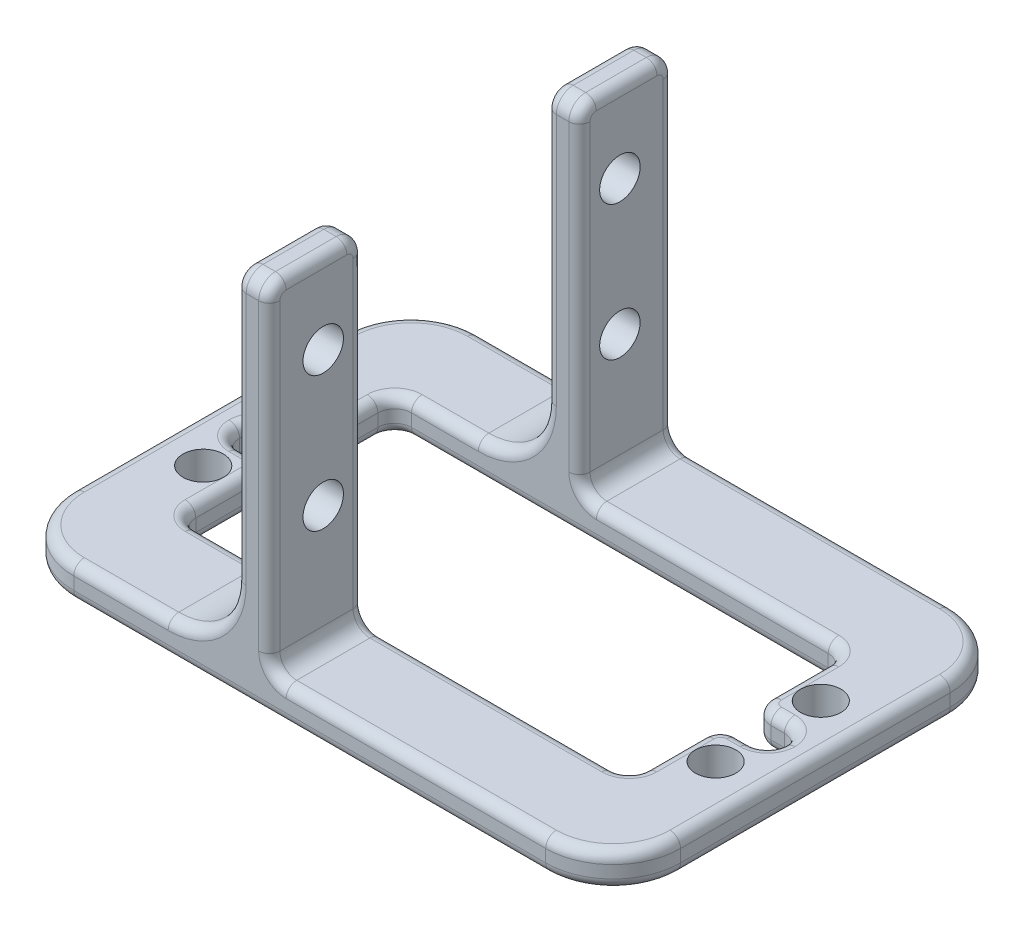
SolidWorks part; units mm, degrees
ref_plane "Front Plane" through (0, 0, 0) normal (0, 0, 1) x (1, 0, 0)
ref_plane "Top Plane" through (0, 0, 0) normal (0, 1, 0) x (1, 0, 0)
ref_plane "Right Plane" through (0, 0, 0) normal (1, 0, 0) x (0, 0, -1)
sketch "Sketch1" plane through (0, 0, 0) normal (0, 1, 0) x (1, 0, 0)
  line L1 (-28.575, -19.05) -> (28.575, -19.05)
  line L2 (-28.575, -19.05) -> (-28.575, 19.05)
  line L3 (-28.575, 19.05) -> (28.575, 19.05)
  line L4 (28.575, -19.05) -> (28.575, 19.05)
  line L5 (-28.575, -19.05) -> (28.575, 19.05) construction
  line L6 (-28.575, 19.05) -> (28.575, -19.05) construction
  point P0 (0, 0)
  dimension "D1" = 38.1
  dimension "D2" = 57.15
extrude "Boss-Extrude1" add sketch "Sketch1" along normal blind 3.175
sketch "Sketch2" plane through (0, 3.175, 0) normal (0, 1, 0) x (1, 0, 0)
  line L0 (0, 0) -> (-28.575, 0) construction
  line L1 (-24.13, -4.953) -> (24.13, -4.953) construction
  line L2 (-24.13, -4.953) -> (-24.13, 4.953) construction
  line L3 (-24.13, 4.953) -> (24.13, 4.953) construction
  line L4 (24.13, -4.953) -> (24.13, 4.953) construction
  line L5 (-24.13, -4.953) -> (24.13, 4.953) construction
  line L6 (-24.13, 4.953) -> (24.13, -4.953) construction
  line L7 (-21.209, -10.16) -> (21.209, -10.16)
  line L8 (-21.209, -10.16) -> (-21.209, 10.16) construction
  line L9 (-21.209, 10.16) -> (21.209, 10.16)
  line L10 (21.209, -10.16) -> (21.209, 10.16) construction
  line L11 (-21.209, -10.16) -> (21.209, 10.16) construction
  line L12 (-21.209, 10.16) -> (21.209, -10.16) construction
  line L13 (-28.575, 19.05) -> (-28.575, -19.05) construction
  line L14 (-28.575, 0) -> (28.575, 0) construction
  line L15 (28.575, -19.05) -> (28.575, 19.05) construction
  line L16 (21.209, -1.5875) -> (21.209, -10.16)
  line L17 (25.654, -1.5875) -> (21.209, -1.5875)
  line L18 (25.654, -1.5875) -> (25.654, 1.5875)
  line L19 (25.654, 1.5875) -> (21.209, 1.5875)
  line L20 (21.209, -1.5875) -> (21.209, 1.5875) construction
  line L21 (25.654, -1.5875) -> (21.209, 1.5875) construction
  line L22 (25.654, 1.5875) -> (21.209, -1.5875) construction
  line L23 (-25.654, -1.5875) -> (-21.209, -1.5875)
  line L24 (-25.654, -1.5875) -> (-25.654, 1.5875)
  line L25 (-25.654, 1.5875) -> (-21.209, 1.5875)
  line L26 (-21.209, -1.5875) -> (-21.209, 1.5875) construction
  line L27 (-25.654, -1.5875) -> (-21.209, 1.5875) construction
  line L28 (-25.654, 1.5875) -> (-21.209, -1.5875) construction
  line L29 (21.209, 1.5875) -> (21.209, 10.16)
  line L30 (-21.209, -10.16) -> (-21.209, -1.5875)
  line L31 (-21.209, 1.5875) -> (-21.209, 10.16)
  circle A0 centre (-24.13, -4.953) radius 1.905
  circle A1 centre (-24.13, 4.953) radius 1.905
  circle A2 centre (24.13, 4.953) radius 1.905
  circle A3 centre (24.13, -4.953) radius 1.905
  point P0 (0, 0)
  point P10 (0, 0)
  point P19 (23.4315, 0)
  point P27 (-23.4315, 0)
  dimension "D3" = 3.81
  dimension "D1" = 48.26
  dimension "D2" = 9.906
  dimension "D4" = 42.418
  dimension "D5" = 20.32
  dimension "D6" = 4.445
  dimension "D7" = 4.445
  dimension "D8" = 3.175
  dimension "D9" = 3.175
extrude "Cut-Extrude1" cut sketch "Sketch2" against normal through all
sketch "Sketch3" plane through (0, 3.175, 0) normal (0, 1, 0) x (1, 0, 0)
  line L0 (-28.575, -19.05) -> (28.575, -19.05) construction
  line L1 (-6.985, -19.05) -> (-3.81, -19.05)
  line L2 (-6.985, -19.05) -> (-6.985, -10.16)
  line L3 (-6.985, -10.16) -> (-3.81, -10.16)
  line L4 (-3.81, -19.05) -> (-3.81, -10.16)
  line L5 (-21.209, -10.16) -> (21.209, -10.16) construction
  line L6 (21.209, 10.16) -> (-21.209, 10.16) construction
  line L7 (-6.985, 10.16) -> (-3.81, 10.16)
  line L8 (-6.985, 10.16) -> (-6.985, 19.05)
  line L9 (-6.985, 19.05) -> (-3.81, 19.05)
  line L10 (-3.81, 10.16) -> (-3.81, 19.05)
  line L11 (28.575, 19.05) -> (-28.575, 19.05) construction
  line L12 (-28.575, 19.05) -> (-28.575, -19.05) construction
  dimension "D1" = 21.59
  dimension "D2" = 3.175
extrude "Boss-Extrude2" add sketch "Sketch3" along normal blind 31.75
sketch "Sketch4" plane through (-6.985, 0, 0) normal (-1, 0, 0) x (0, 0, 1)
  line L0 (13.97, 3.175) -> (13.97, 34.925) construction
  line L1 (10.16, 3.175) -> (19.05, 3.175) construction
  line L2 (10.16, 34.925) -> (19.05, 34.925) construction
  line L3 (-13.97, 34.925) -> (-13.97, 3.175) construction
  line L4 (-19.05, 34.925) -> (-10.16, 34.925) construction
  line L5 (-19.05, 3.175) -> (-10.16, 3.175) construction
  line L6 (0, 0) -> (0, -50000) construction
  line L7 (13.97, 19.05) -> (0, 19.05) construction
  line L8 (0, 19.05) -> (-13.97, 19.05) construction
  circle A0 centre (13.97, 27.305) radius 1.905
  circle A1 centre (-13.97, 27.305) radius 1.905
  circle A2 centre (-13.97, 14.605) radius 1.905
  circle A3 centre (13.97, 14.605) radius 1.905
  dimension "D2" = 3.81
  dimension "D1" = 27.94
  dimension "D3" = 12.7
  dimension "D4" = 11.43
extrude "Cut-Extrude2" cut sketch "Sketch4" against normal through all
fillet "Fillet1" radius 1.5875 18 edges at (-3.81, 3.175, -14.605) (-21.209, 1.5875, -10.16) (-21.209, 1.5875, 10.16) (-21.209, 1.5875, -1.5875) (-21.209, 1.5875, 1.5875) (-25.654, 1.5875, 1.5875) (-25.654, 1.5875, -1.5875) (21.209, 1.5875, -10.16) (21.209, 1.5875, -1.5875) (25.654, 1.5875, -1.5875) (25.654, 1.5875, 1.5875) (21.209, 1.5875, 1.5875) (21.209, 1.5875, 10.16) (-5.3975, 34.925, -10.16) (-5.3975, 34.925, -19.05) (-5.3975, 34.925, 19.05) (-5.3975, 34.925, 10.16)
fillet "Fillet2" radius 6.35 6 edges at (-6.985, 3.175, -14.605) (28.575, 1.5875, 19.05) (28.575, 1.5875, -19.05) (-28.575, 1.5875, -19.05) (-28.575, 1.5875, 19.05)
fillet "Fillet3" radius 1 92 edges at (-26.7151, 0, 17.1901) (-28.575, 0, 0) (-26.7151, 0, -17.1901) (0, 0, -19.05) (26.7151, 0, -17.1901) (28.575, 0, 0) (26.7151, 0, 17.1901) (0, 0, 19.05) (-6.985, 21.4312, -19.05) (-8.8449, 5.0349, -19.05) (-8.8449, 5.0349, 19.05) (-26.7151, 3.175, 17.1901) (-28.575, 3.175, 0) (-26.7151, 3.175, -17.1901) (-3.345, 3.64, 19.05) (26.7151, 3.175, 17.1901) (28.575, 3.175, 0) (26.7151, 3.175, -17.1901) (-3.81, 19.05, -19.05) (-3.345, 3.64, -19.05) (-6.985, 21.4312, -10.16) (-8.8449, 5.0349, -10.16) (-16.4783, 3.175, -10.16) (-20.744, 3.175, -9.695) (-21.209, 3.175, -5.8737) (-21.674, 3.175, -2.0525) (-23.4315, 3.175, -1.5875) (-25.189, 3.175, -1.1225) (-25.189, 3.175, 1.1225) (-23.4315, 3.175, 1.5875) (-21.674, 3.175, 2.0525) (-21.209, 3.175, 5.8738) (-20.744, 3.175, 9.695) (-8.8449, 5.0349, 10.16) (-3.345, 3.64, 10.16) (-3.81, 19.05, -10.16) (-3.345, 3.64, -10.16) (8.6995, 3.175, -10.16) (20.744, 3.175, -9.695) (21.209, 3.175, -5.8737) (21.674, 3.175, -2.0525) (23.4315, 3.175, -1.5875) (25.189, 3.175, -1.1225) (25.189, 3.175, 1.1225) (23.4315, 3.175, 1.5875) (21.674, 3.175, 2.0525) (21.209, 3.175, 5.8738) (20.744, 3.175, 9.695) (-20.744, 0, 9.695) (-21.209, 0, 5.8738) (-21.674, 0, 2.0525) (-23.4315, 0, 1.5875) (-25.189, 0, 1.1225) (-25.189, 0, -1.1225) (-23.4315, 0, -1.5875) (-21.674, 0, -2.0525) (-21.209, 0, -5.8737) (-20.744, 0, -9.695) (0, 0, -10.16) (20.744, 0, -9.695) (21.209, 0, -5.8737) (21.674, 0, -2.0525) (23.4315, 0, -1.5875) (25.189, 0, -1.1225) (25.189, 0, 1.1225) (23.4315, 0, 1.5875) (21.674, 0, 2.0525) (21.209, 0, 5.8738) (20.744, 0, 9.695) (-17.78, 3.175, -19.05) (10.0013, 3.175, -19.05) (0, 0, 10.16) (-6.985, 34.46, -10.625) (-6.985, 34.925, -14.605) (-6.985, 34.46, -18.585) (-6.985, 34.46, 18.585) (-6.985, 34.925, 14.605) (-6.985, 34.46, 10.625) (-3.81, 34.46, 10.625) (-3.81, 34.925, 14.605) (-3.81, 34.46, 18.585) (-3.81, 34.46, -18.585) (-3.81, 34.925, -14.605) (-3.81, 34.46, -10.625)
